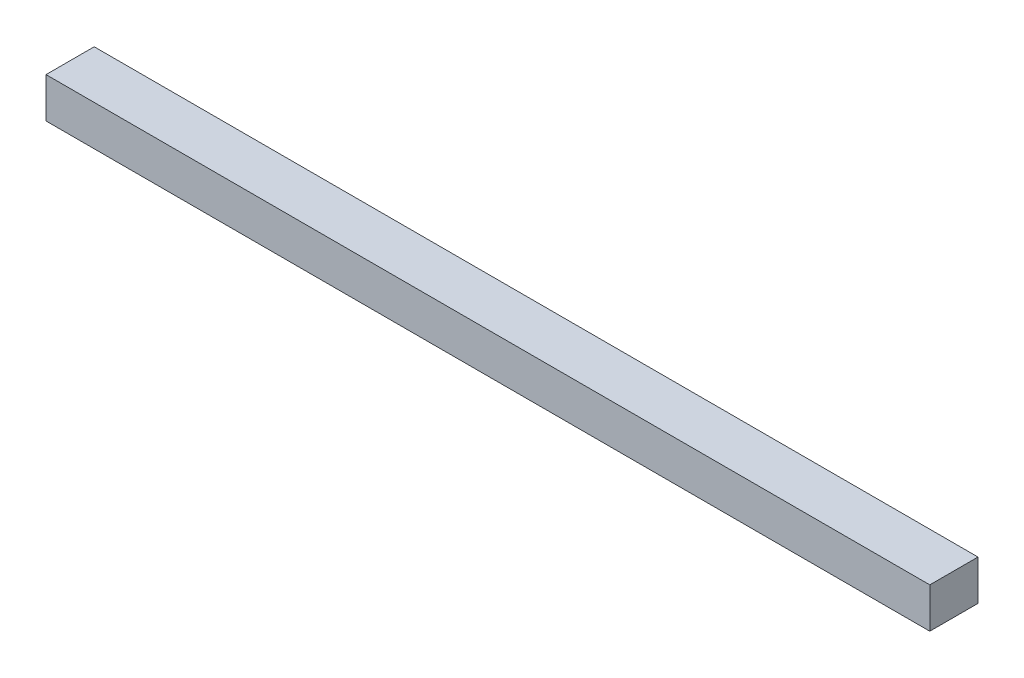
SolidWorks part; units mm, degrees
ref_plane "Спереди" through (0, 0, 0) normal (0, 0, 1) x (1, 0, 0)
ref_plane "Сверху" through (0, 0, 0) normal (0, 1, 0) x (1, 0, 0)
ref_plane "Справа" through (0, 0, 0) normal (1, 0, 0) x (0, 0, -1)
sketch "Эскиз2" plane through (0, 0, 0) normal (1, 0, 0) x (0, 0, -1)
  line L1 (-15, -12.5) -> (15, -12.5)
  line L2 (-15, -12.5) -> (-15, 12.5)
  line L3 (-15, 12.5) -> (15, 12.5)
  line L4 (15, -12.5) -> (15, 12.5)
  line L5 (-15, -12.5) -> (15, 12.5) construction
  line L6 (-15, 12.5) -> (15, -12.5) construction
  point P0 (0, 0)
extrude "Бобышка-Вытянуть1" add sketch "Эскиз2" along normal blind 550
